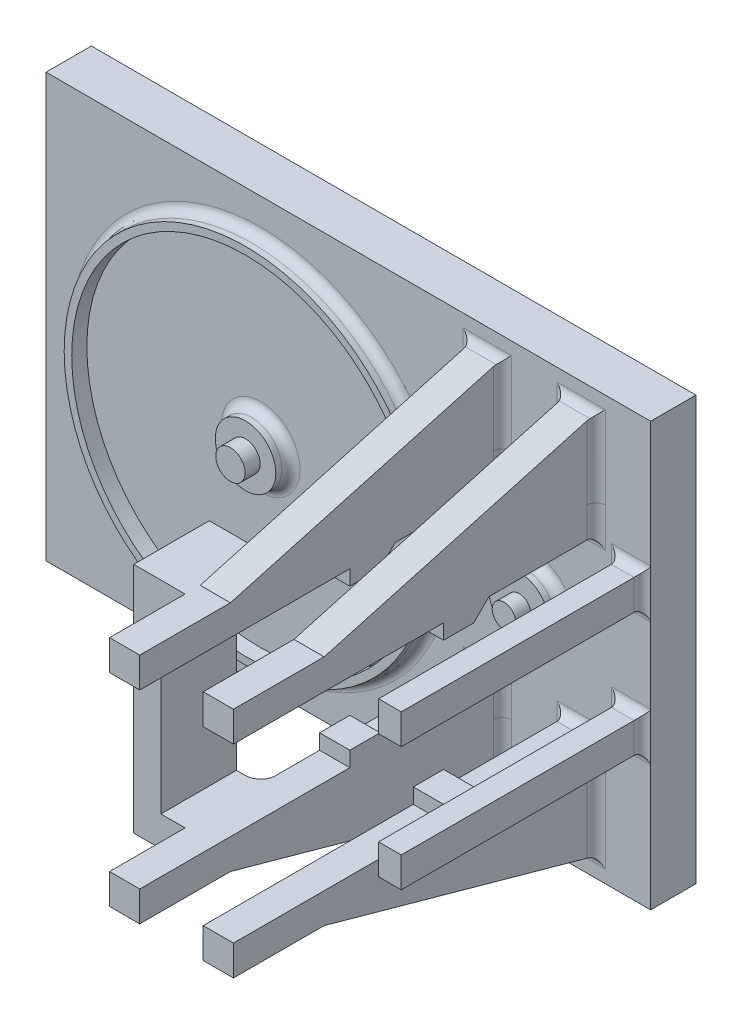
SolidWorks part; units mm, degrees
ref_plane "Front Plane" through (0, 0, 0) normal (0, 0, 1) x (1, 0, 0)
ref_plane "Top Plane" through (0, 0, 0) normal (0, 1, 0) x (1, 0, 0)
ref_plane "Right Plane" through (0, 0, 0) normal (1, 0, 0) x (0, 0, -1)
sketch "Sketch3" plane through (0, 0, 0) normal (0, 0, 1) x (1, 0, 0)
  line L1 (0, 0) -> (200, 0)
  line L2 (0, 0) -> (0, 140)
  line L3 (0, 140) -> (200, 140)
  line L4 (200, 0) -> (200, 140)
  dimension "D1" = 140
  dimension "D2" = 200
extrude "Boss-Extrude1" add sketch "Sketch3" against normal blind 15
sketch "Sketch4" plane through (0, 0, 0) normal (0, 0, 1) x (1, 0, 0)
  line L0 (200, 140) -> (0, 140) construction
  line L1 (190, 98.5) -> (133, 98.5)
  line L2 (190, 98.5) -> (190, 41.5)
  line L3 (190, 41.5) -> (133, 41.5)
  line L4 (133, 98.5) -> (133, 41.5)
  line L5 (200, 0) -> (200, 140) construction
  line L8 (141, 98.5) -> (151, 98.5)
  line L9 (141, 98.5) -> (141, 103.5)
  line L10 (141, 103.5) -> (151, 103.5)
  line L11 (151, 98.5) -> (151, 103.5)
  line L12 (172, 98.5) -> (182, 98.5)
  line L13 (172, 98.5) -> (172, 103.5)
  line L14 (172, 103.5) -> (182, 103.5)
  line L15 (182, 98.5) -> (182, 103.5)
  line L16 (141, 41.5) -> (151, 41.5)
  line L17 (141, 41.5) -> (141, 36.5)
  line L18 (141, 36.5) -> (151, 36.5)
  line L19 (151, 41.5) -> (151, 36.5)
  line L20 (172, 41.5) -> (182, 41.5)
  line L21 (172, 41.5) -> (172, 36.5)
  line L22 (172, 36.5) -> (182, 36.5)
  line L23 (182, 41.5) -> (182, 36.5)
  line L24 (190, 44.5) -> (195, 44.5)
  line L25 (190, 44.5) -> (190, 54.5)
  line L26 (190, 54.5) -> (195, 54.5)
  line L27 (195, 44.5) -> (195, 54.5)
  line L28 (190, 95.5) -> (195, 95.5)
  line L29 (190, 95.5) -> (190, 85.5)
  line L30 (190, 85.5) -> (195, 85.5)
  line L31 (195, 95.5) -> (195, 85.5)
  circle A0 centre (161.5, 70) radius 10
  circle A1 centre (71, 70) radius 10
  dimension "D1" = 20
  dimension "D2" = 20
  dimension "D3" = 90.5
  dimension "D4" = 57
  dimension "D5" = 57
  dimension "D6" = 28.5
  dimension "D7" = 67
  dimension "D8" = 41.5
  dimension "D9" = 70
  dimension "D10" = 10
  dimension "D11" = 5
  dimension "D12" = 10
  dimension "D13" = 5
  dimension "D14" = 10
  dimension "D15" = 5
  dimension "D16" = 10
  dimension "D17" = 5
  dimension "D18" = 10
  dimension "D19" = 5
  dimension "D20" = 5
  dimension "D21" = 10
  dimension "D22" = 8
  dimension "D23" = 8
  dimension "D24" = 3
  dimension "D25" = 3
  dimension "D26" = 8
  dimension "D27" = 8
extrude "Boss-Extrude5" add sketch "Sketch4" along normal blind 70 contours L24 L27 L26 L2 | L31 L28 L2 L30 | L1 L15 L14 L13 | L1 L11 L10 L9 | L19 L3 L17 L18 | L23 L3 L21 L22 region at (177, 101, 0) region at (192.5, 90.5, 0) region at (146, 101, 0) region at (192.5, 49.5, 0) region at (177, 39, 0) region at (146, 39, 0)
sketch "Sketch8" plane through (0, 98.5, 0) normal (0, -1, 0) x (1, 0, 0)
  line L0 (141, 70) -> (141, 0) construction
  line L1 (141, 45.5) -> (151, 45.5)
  line L2 (141, 45.5) -> (141, 35.5)
  line L3 (141, 35.5) -> (151, 35.5)
  line L4 (151, 45.5) -> (151, 35.5)
  line L5 (151, 70) -> (151, 0) construction
  line L6 (172, 70) -> (172, 0) construction
  line L7 (172, 45.5) -> (182, 45.5)
  line L8 (172, 45.5) -> (172, 35.5)
  line L9 (172, 35.5) -> (182, 35.5)
  line L10 (182, 45.5) -> (182, 35.5)
  line L11 (182, 70) -> (182, 0) construction
  line L12 (151, 0) -> (141, 0) construction
  line L13 (182, 0) -> (172, 0) construction
  dimension "D1" = 45.5
  dimension "D2" = 45.5
  dimension "D3" = 10
  dimension "D4" = 10
extrude "Boss-Extrude6" add sketch "Sketch8" along normal blind 5
sketch "Sketch9" plane through (141, 0, 0) normal (-1, 0, 0) x (0, 0, 1)
  line L2 (45.5, 93.5) -> (35.5, 93.5) construction
  line L3 (40.5, 93.5) -> (35.5, 93.5)
  line L4 (35.5, 93.5) -> (35.5, 98.5)
  line L5 (35.5, 98.5) -> (40.5, 93.5)
  dimension "D1" = 5
extrude "Cut-Extrude2" cut sketch "Sketch9" against normal up to surface (41 mm away) up to face at (182, 98.5, 37.75)
sketch "Sketch10" plane through (0, 41.5, 0) normal (0, 1, 0) x (1, 0, 0)
  line L0 (141, -70) -> (141, 0) construction
  line L1 (141, -35.5) -> (151, -35.5)
  line L2 (141, -35.5) -> (141, -45.5)
  line L3 (141, -45.5) -> (151, -45.5)
  line L4 (151, -35.5) -> (151, -45.5)
  line L5 (151, -70) -> (151, 0) construction
  line L6 (172, -70) -> (172, 0) construction
  line L7 (172, -35.5) -> (182, -35.5)
  line L8 (172, -35.5) -> (172, -45.5)
  line L9 (172, -45.5) -> (182, -45.5)
  line L10 (182, -35.5) -> (182, -45.5)
  line L11 (182, -70) -> (182, 0) construction
  line L12 (151, 0) -> (141, 0) construction
  line L13 (182, 0) -> (172, 0) construction
  dimension "D1" = 45.5
  dimension "D2" = 10
  dimension "D3" = 10
  dimension "D4" = 45.5
extrude "Boss-Extrude7" add sketch "Sketch10" along normal blind 5
sketch "Sketch11" plane through (141, 0, 0) normal (-1, 0, 0) x (0, 0, 1)
  line L0 (35.5, 41.5) -> (40.5, 46.5)
  line L1 (35.5, 46.5) -> (45.5, 46.5) construction
  line L2 (40.5, 46.5) -> (35.5, 46.5)
  line L3 (35.5, 46.5) -> (35.5, 41.5) construction
  line L4 (35.5, 46.5) -> (35.5, 41.5)
extrude "Cut-Extrude3" cut sketch "Sketch11" against normal up to surface (41 mm away) up to face at (182, 41.5, 37.75)
sketch "Sketch12" plane through (0, 0, 0) normal (0, 0, 1) x (1, 0, 0)
  line L0 (200, 0) -> (200, 140) construction
  circle A0 centre (161.5, 68.1112) radius 10
  circle A1 centre (71, 68.1112) radius 10
  dimension "D1" = 20
  dimension "D2" = 20
  dimension "D3" = 90.5
  dimension "D4" = 38.5
extrude "Boss-Extrude8" add sketch "Sketch12" along normal blind 5
sketch "Sketch13" plane through (0, 0, 5) normal (0, 0, 1) x (1, 0, 0)
  circle A0 centre (71, 68.1112) radius 4.85
  circle A1 centre (161.5, 68.1112) radius 3.85
  dimension "D1" = 9.7
  dimension "D2" = 7.7
extrude "Boss-Extrude9" add sketch "Sketch13" along normal blind 5
sketch "Sketch14" plane through (0, 0, 70) normal (0, 0, 1) x (1, 0, 0)
  line L1 (190, 95.5) -> (195, 95.5)
  line L2 (190, 95.5) -> (190, 85.5)
  line L3 (190, 85.5) -> (195, 85.5)
  line L4 (195, 95.5) -> (195, 85.5)
  line L5 (190, 54.5) -> (195, 54.5)
  line L6 (190, 54.5) -> (190, 44.5)
  line L7 (190, 44.5) -> (195, 44.5)
  line L8 (195, 54.5) -> (195, 44.5)
extrude "Cut-Extrude4" cut sketch "Sketch14" against normal blind 20
sketch "Sketch15" plane through (0, 0, 0) normal (0, 0, 1) x (1, 0, 0)
  circle A0 centre (71, 68.1112) radius 57.5
  circle A1 centre (71, 68.1112) radius 60
  dimension "D1" = 120
  dimension "D2" = 115
sketch "Sketch16" plane through (0, 0, 0) normal (0, 0, 1) x (1, 0, 0)
  line L1 (141, 103.5) -> (151, 103.5)
  line L2 (141, 103.5) -> (141, 108.5)
  line L3 (141, 108.5) -> (151, 108.5)
  line L4 (151, 103.5) -> (151, 108.5)
  line L5 (172, 103.5) -> (182, 103.5)
  line L6 (172, 103.5) -> (172, 108.5)
  line L7 (172, 108.5) -> (182, 108.5)
  line L8 (182, 103.5) -> (182, 108.5)
  line L9 (195, 95.5) -> (197.5, 95.5)
  line L10 (195, 95.5) -> (195, 85.5)
  line L11 (195, 85.5) -> (197.5, 85.5)
  line L12 (197.5, 95.5) -> (197.5, 85.5)
  line L13 (141, 36.5) -> (151, 36.5)
  line L14 (141, 36.5) -> (141, 31.5)
  line L15 (141, 31.5) -> (151, 31.5)
  line L16 (151, 36.5) -> (151, 31.5)
  line L17 (172, 36.5) -> (182, 36.5)
  line L18 (172, 36.5) -> (172, 31.5)
  line L19 (172, 31.5) -> (182, 31.5)
  line L20 (182, 36.5) -> (182, 31.5)
  line L21 (195, 54.5) -> (197.5, 54.5)
  line L22 (195, 54.5) -> (195, 44.5)
  line L23 (195, 44.5) -> (197.5, 44.5)
  line L24 (197.5, 54.5) -> (197.5, 44.5)
  dimension "D1" = 10
  dimension "D2" = 5
  dimension "D3" = 10
  dimension "D4" = 5
  dimension "D5" = 2.5
  dimension "D6" = 10
  dimension "D7" = 10
  dimension "D8" = 2.5
  dimension "D9" = 10
  dimension "D10" = 5
  dimension "D11" = 5
  dimension "D12" = 10
extrude "Boss-Extrude11" add sketch "Sketch16" along normal up to surface (70 mm away) up to face at (177, 101, 70)
sketch "Sketch17" plane through (0, 0, 50) normal (0, 0, 1) x (1, 0, 0)
  line L1 (190, 95.5) -> (195, 95.5)
  line L2 (190, 95.5) -> (190, 85.5)
  line L3 (190, 85.5) -> (195, 85.5)
  line L4 (195, 95.5) -> (195, 85.5)
  line L5 (190, 54.5) -> (195, 54.5)
  line L6 (190, 54.5) -> (190, 44.5)
  line L7 (190, 44.5) -> (195, 44.5)
  line L8 (195, 54.5) -> (195, 44.5)
extrude "Boss-Extrude12" add sketch "Sketch17" along normal up to surface (20 mm away) up to face at (196.25, 90.5, 70)
fillet "Fillet1" radius 3 20 edges at (190, 49.5, 0) (190, 90.5, 0) (177, 98.5, 0) (146, 98.5, 0) (177, 41.5, 0) (146, 41.5, 0) (141, 103.5, 0) (151, 103.5, 0) (172, 103.5, 0) (182, 103.5, 0) (193.75, 95.5, 0) (197.5, 90.5, 0) (193.75, 85.5, 0) (193.75, 54.5, 0) (197.5, 49.5, 0) (193.75, 44.5, 0) (182, 36.5, 0) (172, 36.5, 0) (151, 36.5, 0) (141, 36.5, 0)
sketch "Sketch18" plane through (0, 0, 70) normal (0, 0, 1) x (1, 0, 0)
  line L1 (141, 108.5) -> (151, 108.5)
  line L2 (141, 108.5) -> (141, 98.5)
  line L3 (141, 98.5) -> (151, 98.5)
  line L4 (151, 108.5) -> (151, 98.5)
  line L5 (172, 108.5) -> (182, 108.5)
  line L6 (172, 108.5) -> (172, 98.5)
  line L7 (172, 98.5) -> (182, 98.5)
  line L8 (182, 108.5) -> (182, 98.5)
  line L9 (141, 41.5) -> (151, 41.5)
  line L10 (141, 41.5) -> (141, 31.5)
  line L11 (141, 31.5) -> (151, 31.5)
  line L12 (151, 41.5) -> (151, 31.5)
  line L13 (172, 41.5) -> (182, 41.5)
  line L14 (172, 41.5) -> (172, 31.5)
  line L15 (172, 31.5) -> (182, 31.5)
  line L16 (182, 41.5) -> (182, 31.5)
extrude "Boss-Extrude13" add sketch "Sketch18" along normal blind 50
sketch "Sketch19" plane through (0, 0, 45.5) normal (0, 0, 1) x (1, 0, 0)
  line L1 (141, 98.5) -> (151, 98.5)
  line L2 (141, 98.5) -> (141, 93.5)
  line L3 (141, 93.5) -> (151, 93.5)
  line L4 (151, 98.5) -> (151, 93.5)
  line L5 (172, 98.5) -> (182, 98.5)
  line L6 (172, 98.5) -> (172, 93.5)
  line L7 (172, 93.5) -> (182, 93.5)
  line L8 (182, 98.5) -> (182, 93.5)
  line L9 (172, 46.5) -> (182, 46.5)
  line L10 (172, 46.5) -> (172, 41.5)
  line L11 (172, 41.5) -> (182, 41.5)
  line L12 (182, 46.5) -> (182, 41.5)
  line L13 (141, 46.5) -> (151, 46.5)
  line L14 (141, 46.5) -> (141, 41.5)
  line L15 (141, 41.5) -> (151, 41.5)
  line L16 (151, 46.5) -> (151, 41.5)
extrude "Boss-Extrude14" add sketch "Sketch19" along normal blind 5
fillet "Fillet3" radius 3 1 edges at (61, 68.1112, 0)
sketch "Sketch20" plane through (0, 0, 70) normal (0, 0, 1) x (1, 0, 0)
  line L1 (190, 95.5) -> (197.5, 95.5)
  line L2 (190, 95.5) -> (190, 85.5)
  line L3 (190, 85.5) -> (197.5, 85.5)
  line L4 (197.5, 95.5) -> (197.5, 85.5)
  line L5 (190, 54.5) -> (197.5, 54.5)
  line L6 (190, 54.5) -> (190, 44.4997)
  line L7 (190, 44.4997) -> (197.5, 44.4997)
  line L8 (197.5, 54.5) -> (197.5, 44.4997)
extrude "Boss-Extrude16" add sketch "Sketch20" along normal blind 10
sketch "Sketch21" plane through (182, 0, 0) normal (1, 0, 0) x (0, 0, -1)
  line L0 (-90, 31.5) -> (0, 6.5)
  line L2 (0, 6.5) -> (0, 31.5)
  line L3 (0, 31.5) -> (-90, 31.5)
  line L4 (-90, 108.5) -> (0, 133.5)
  line L5 (-120, 108.5) -> (-3, 108.5) construction
  line L6 (0, 98.5) -> (0, 140) construction
  line L7 (0, 133.5) -> (0, 108.5)
  line L8 (0, 108.5) -> (-90, 108.5)
  dimension "D1" = 25
  dimension "D2" = 90
  dimension "D3" = 25
  dimension "D4" = 90
extrude "Boss-Extrude17" add sketch "Sketch21" against normal up to surface (41 mm away) up to face at (141, 99.75, 52.875)
sketch "Sketch22" plane through (0, 108.5, 0) normal (0, -1, 0) x (1, 0, 0)
  line L0 (154, 0) -> (169, 0) construction
  line L1 (151, 90) -> (172, 90)
  line L2 (151, 90) -> (151, 0)
  line L3 (151, 0) -> (172, 0)
  line L4 (172, 90) -> (172, 0)
extrude "Cut-Extrude6" cut sketch "Sketch22" against normal through all
sketch "Sketch23" plane through (0, 31.5, 0) normal (0, 1, 0) x (1, 0, 0)
  line L1 (172, -90) -> (151, -90)
  line L2 (172, -90) -> (172, 0)
  line L3 (172, 0) -> (151, 0)
  line L4 (151, -90) -> (151, 0)
extrude "Cut-Extrude7" cut sketch "Sketch23" against normal through all
fillet "Fillet4" radius 3 12 edges at (177, 6.5, 0) (146, 6.5, 0) (172, 19, 0) (151, 19, 0) (141, 19, 0) (141, 121, 0) (146, 133.5, 0) (151, 121, 0) (172, 121, 0) (177, 133.5, 0) (182, 121, 0) (182, 19, 0)
sketch "Sketch25" plane through (0, 0, 120) normal (0, 0, 1) x (1, 0, 0)
  line L0 (187, 98.5) -> (200, 98.5) construction
  line L1 (190, 98.5) -> (133, 98.5)
  line L2 (190, 98.5) -> (190, 41.5)
  line L3 (190, 41.5) -> (133, 41.5)
  line L4 (133, 98.5) -> (133, 41.5)
  line L5 (141, 98.5) -> (141, 108.5)
  line L6 (141, 108.5) -> (124, 108.5)
  line L7 (124, 108.5) -> (124, 31.5)
  line L8 (124, 31.5) -> (141, 31.5)
  line L9 (141, 31.5) -> (141, 7.3333) construction
  line L10 (141, 31.5) -> (141, 41.5)
  line L11 (141, 31.5) -> (151, 31.5) construction
  line L15 (190, 95.5) -> (190, 85.5) construction
  line M3 (141, 108.5) -> (141, 98.5)
  dimension "D1" = 57
  dimension "D2" = 57
  dimension "D4" = 9
extrude "Boss-Extrude19" add sketch "Sketch25" against normal blind 50 contours L8 L10 L3 L4 L1 L6 L7 M3 region at (130.0944, 70, 120)
sketch "Sketch26" plane through (0, 0, 120) normal (0, 0, 1) x (1, 0, 0)
  line L0 (141, 108.5) -> (141, 98.5)
  line L1 (141, 98.5) -> (133, 98.5)
  line L2 (133, 98.5) -> (133, 41.5)
  line L3 (133, 41.5) -> (141, 41.5)
  line L4 (141, 41.5) -> (141, 31.5)
  line L5 (141, 31.5) -> (124, 31.5)
  line L6 (124, 31.5) -> (124, 108.5)
  line L7 (124, 108.5) -> (141, 108.5)
extrude "Cut-Extrude9" cut sketch "Sketch26" against normal blind 25
fillet "Fillet5" radius 5 2 edges at (141, 36.5, 70) (141, 103.5, 70)
sketch "Sketch28" plane through (0, 0, 10) normal (0, 0, 1) x (1, 0, 0)
  circle A0 centre (161.5, 68.1112) radius 13
extrude "Cut-Extrude10" cut sketch "Sketch28" against normal up to surface (10 mm away) up to face at (162.3333, 70, 0)
sketch "Sketch29" plane through (0, 0, 0) normal (0, 0, 1) x (1, 0, 0)
  line L0 (200, 41.5) -> (187, 41.5) construction
  line L1 (133, 98.5) -> (190, 98.5)
  line L3 (133, 41.5) -> (190, 41.5)
  line L4 (190, 98.5) -> (190, 41.5)
  circle A0 centre (161.5, 70) radius 10
  dimension "D3" = 20
  dimension "D1" = 28.5
  dimension "D2" = 28.5
extrude "Boss-Extrude21" add sketch "Sketch29" along normal up to surface (5 mm away) contours A0 region at (161.5, 70, 0) up to face at (75.85, 68.1112, 5)
sketch "Sketch30" plane through (0, 0, 5) normal (0, 0, 1) x (1, 0, 0)
  circle A0 centre (161.5, 70) radius 3.9
  dimension "D1" = 7.8
extrude "Boss-Extrude22" add sketch "Sketch30" along normal up to surface (5 mm away) up to face at (75.85, 68.1112, 10)
fillet "Fillet6" radius 3 1 edges at (151.5, 70, 0)
extrude "Boss-Extrude23" add sketch "Sketch15" along normal up to surface (5 mm away) up to face at (75.85, 68.1112, 5)
fillet "Fillet7" radius 3 1 edges at (11, 68.1112, 0)
equation "\"D6@Sketch4\"=57/2"
equation "\"D8@Sketch4\"=70-28.5"
